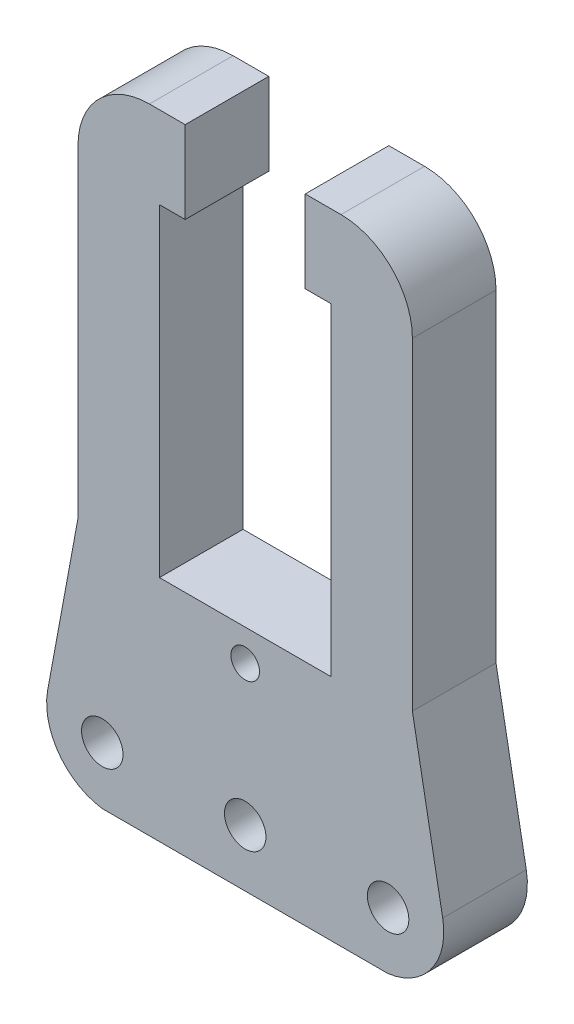
SolidWorks part; units mm, degrees
material "Acrylic (Medium-high impact)"
ref_plane "Front Plane" through (0, 0, 0) normal (0, 0, 1) x (1, 0, 0)
ref_plane "Top Plane" through (0, 0, 0) normal (0, 1, 0) x (1, 0, 0)
ref_plane "Right Plane" through (0, 0, 0) normal (1, 0, 0) x (0, 0, -1)
sketch "Model" plane through (0, 0, 0) normal (0, 0, 1) x (1, 0, 0)
  line L0 (519.9822, -457.799) -> (519.9822, 49542.201) construction
  line L1 (508.2822, 554.9348) -> (506.1623, 543.4616)
  line L2 (519.9822, 542.1848) -> (509.9822, 542.1848) construction
  line L3 (513.9822, 554.1848) -> (525.9822, 554.1848)
  line L4 (509.9822, 538.1848) -> (529.9822, 538.1848)
  line L5 (508.2822, 577.5348) -> (508.2822, 554.9348)
  line L6 (515.7822, 582.5348) -> (513.2822, 582.5348)
  line L7 (515.7822, 576.7848) -> (515.7822, 582.5348)
  line L8 (513.9822, 576.7848) -> (515.7822, 576.7848)
  line L9 (513.9822, 554.1848) -> (513.9822, 576.7848)
  line L10 (519.9822, 542.1848) -> (529.9822, 542.1848) construction
  line L80 (525.9822, 554.1848) -> (525.9822, 576.7848)
  line L81 (525.9822, 576.7848) -> (524.1822, 576.7848)
  line L82 (524.1822, 576.7848) -> (524.1822, 582.5348)
  line L83 (524.1822, 582.5348) -> (526.6822, 582.5348)
  line L84 (531.6822, 577.5348) -> (531.6822, 554.9348)
  line L85 (531.6822, 554.9348) -> (533.8022, 543.4616)
  circle A0 centre (509.9822, 542.1848) radius 1.45
  arc A1 (526.6822, 582.5348) -> (531.6822, 577.5348) centre (526.6822, 577.5348) cw
  arc A2 (506.1623, 543.4616) -> (509.9822, 538.1848) centre (510.5874, 542.644) ccw
  arc A3 (533.8022, 543.4616) -> (529.9822, 538.1848) centre (529.3771, 542.644) cw
  arc A4 (513.2822, 582.5348) -> (508.2822, 577.5348) centre (513.2822, 577.5348) ccw
  circle A5 centre (519.9822, 542.1848) radius 1.45
  circle A6 centre (529.9822, 542.1848) radius 1.45
  circle A7 centre (519.9822, 551.9848) radius 1
  point P2 (519.9822, 554.1848)
  point P5 (519.9822, 538.1848)
  point P6 (519.9822, 554.1848)
  point P13 (519.9822, 538.1848)
  dimension "D4" = 2.9
  dimension "D9" = 4.5
  dimension "D11" = 5
  dimension "D14" = 2
  dimension "D2" = 22.6
  dimension "D3" = 10
  dimension "D5" = 4
  dimension "D1" = 12
  dimension "D6" = 12
  dimension "D7" = 5.75
  dimension "D8" = 1.8
  dimension "D10" = 11.4732
  dimension "D12" = 20
  dimension "D13" = 2.5
  dimension "D15" = 2.2
extrude "Boss-Extrude1" add sketch "Model" along normal blind 5.85
equation "\"D1@Model\"=\"Servo_width@Servo-1.Part\""
equation "\"D2@Model\"=\"Servo_length@Servo-1.Part\""
